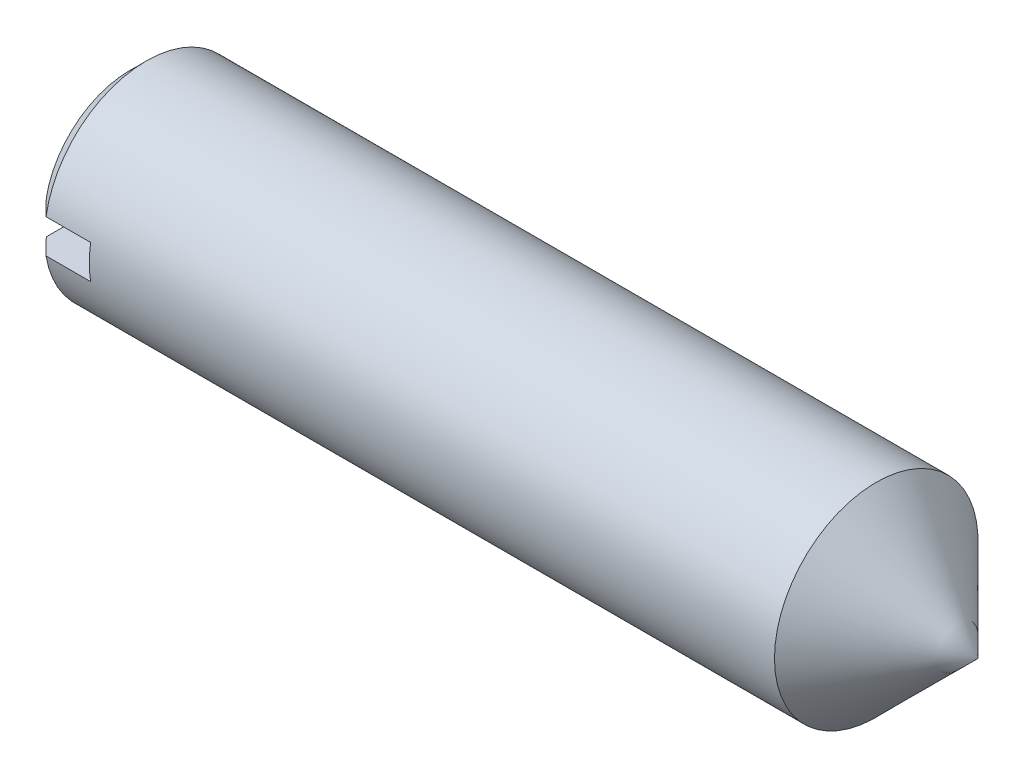
SolidWorks part; units mm, degrees
ref_plane "Front Plane" through (0, 0, 0) normal (0, 0, 1) x (1, 0, 0)
ref_plane "Top Plane" through (0, 0, 0) normal (0, 1, 0) x (1, 0, 0)
ref_plane "Right Plane" through (0, 0, 0) normal (1, 0, 0) x (0, 0, -1)
sketch "BodySke" plane through (0, 0, 0) normal (0, 0, 1) x (1, 0, 0)
  line L0 (0, 0) -> (88.3411, 0) construction
  line L1 (0, 0) -> (0, 5.036)
  line L2 (0, 5.036) -> (0.964, 6)
  line L3 (0.964, 6) -> (44, 6)
  line L4 (50, 0) -> (44, 6)
  line L5 (0.964, -6) -> (44, -6) construction
  line L6 (50, 0) -> (0, 0)
  line L7 (1.75, 0) -> (1.75, 8.5388) construction
  line L8 (0, -5.036) -> (0.964, -6) construction
  line L9 (50, 0) -> (44, -6) construction
  dimension "Thread_minor" = 10.072
  dimension "Length" = 50
  dimension "Drive_chamfer_angle" = 90
  dimension "Advance" = 1.75
revolve "BaseBody" add sketch "BodySke" angle 360 about L0
cosmetic thread "ThreadCosmetic" [suppressed] parameters "Thread_minor"=10.072
sketch "SlotSke" plane through (0, 0, 0) normal (1, 0, 0) x (0, 0, -1)
  line L0 (-6, 1) -> (6, -1) construction
  line L1 (-6, 1) -> (6, 1)
  line L2 (-6, 1) -> (-6, -1)
  line L3 (-6, -1) -> (6, -1)
  line L4 (6, 1) -> (6, -1)
  dimension "D1" = 12
extrude "Slot" cut sketch "SlotSke" along normal blind 3.6
sketch "ThdSchSke" plane through (0, 0, 0) normal (0, 0, 1) x (1, 0, 0)
  line L0 (0, 0) -> (53.6961, 0) construction
  line L1 (1.6009, 7.1131) -> (1.6009, 6)
  line L2 (1.6009, 7.1131) -> (2.714, 7.1131)
  line L3 (2.714, 7.1131) -> (2.714, 6)
  line L4 (2.714, 6) -> (2.1574, 5.036)
  line L5 (2.1574, 5.036) -> (1.6009, 6)
  dimension "D1" = 1.75
revolve "ThreadSchematic" [suppressed] cut sketch "ThdSchSke" angle 360 about L0
pattern_linear "ThdSchPat" [suppressed] of bodies 115
equation "\"Thread_minor@ThreadCosmetic\" = \"Thread_minor@BodySke\""
equation "\"D1@SlotSke\" = \"Diameter@BodySke\""
equation "\"D1@ThdSchSke\" = \"Advance@BodySke\""
equation "\"Advance@ThdSchPat\" = \"Advance@BodySke\""
equation "\"Tooth_Num@ThdSchPat\" =  int( \"Length@BodySke\" / \"Advance@BodySke\" )  - 1"
